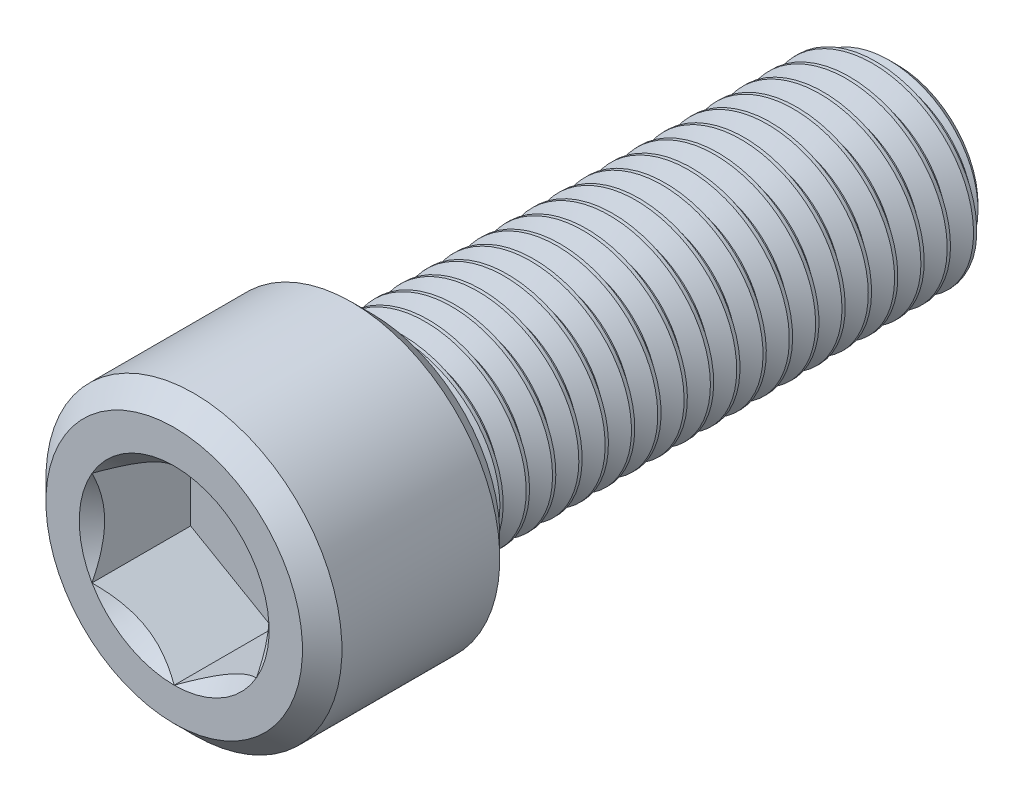
SolidWorks part; units mm, degrees
ref_plane "Front Plane" through (0, 0, 0) normal (0, 0, 1) x (1, 0, 0)
ref_plane "Top Plane" through (0, 0, 0) normal (0, 1, 0) x (1, 0, 0)
ref_plane "Right Plane" through (0, 0, 0) normal (1, 0, 0) x (0, 0, -1)
sketch "Sketch1" plane through (0, 0, 0) normal (1, 0, 0) x (0, 0, -1)
  line L0 (34.925, 0) -> (-34.925, 0) construction
  line L1 (-34.925, 0) -> (-34.925, 12.3825)
  line L2 (-34.925, 12.3825) -> (-33.02, 14.2875)
  line L3 (-33.02, 14.2875) -> (-17.78, 14.2875)
  line L4 (-17.78, 14.2875) -> (-15.875, 12.3825)
  line L5 (-15.875, 12.3825) -> (-15.875, 9.525)
  line L6 (-15.875, 9.525) -> (33.147, 9.525)
  line L7 (33.147, 9.525) -> (34.925, 7.747)
  line L8 (34.925, 7.747) -> (34.925, 0)
  line L9 (34.7662, 9.8) -> (37.3063, 9.8) construction
  line L10 (37.3063, 9.8) -> (36.0363, 7.6003) construction
  line L11 (36.0363, 7.6003) -> (34.7662, 9.8) construction
  line L12 (34.925, 9.525) -> (37.1475, 9.525) construction
  line L13 (36.0363, 9.8) -> (36.0362, 9.525) construction
  line L14 (35.8775, 7.8752) -> (36.195, 7.8752) construction
  line L15 (36.0362, 7.8752) -> (36.0363, 7.6003) construction
  line L16 (34.8456, 9.6625) -> (37.2269, 9.6625)
  line L17 (37.2269, 9.6625) -> (36.195, 7.8752)
  line L18 (36.195, 7.8752) -> (35.8775, 7.8752)
  line L19 (35.8775, 7.8752) -> (34.8456, 9.6625)
  line L20 (33.147, -9.525) -> (28.575, -9.525) construction
  point P3 (-32.0675, 14.2875)
  point P4 (0, 0)
  point P25 (36.0363, 9.6625)
  point P26 (34.925, 9.525)
  point P28 (-18.7325, 14.2875)
  point P29 (-25.4, 14.2875)
  point P33 (28.575, -9.525)
  dimension "Head Ht" = 19.05
  dimension "Screw Size" = 19.05
  dimension "Head Dia" = 28.575
  dimension "D1" = 45
  dimension "D2" = 45
  dimension "D3" = 1.905
  dimension "D4" = 1.905
  dimension "Pitch" = 2.54
  dimension "D5" = 0.3175
  dimension "D6" = 1.778
  dimension "D7" = 4.572
  dimension "Length" = 50.8
  dimension "D8" = 0.9525
  dimension "D9" = 0.9525
sketch "Sketch2" plane through (0, 0, 0) normal (0, 0, 1) x (1, 0, 0)
  line L1 (0, 9.1654) -> (-7.9375, 4.5827)
  line L2 (-7.9375, 4.5827) -> (-7.9375, -4.5827)
  line L3 (-7.9375, -4.5827) -> (0, -9.1654)
  line L4 (0, -9.1654) -> (7.9375, -4.5827)
  line L5 (7.9375, -4.5827) -> (7.9375, 4.5827)
  line L6 (7.9375, 4.5827) -> (0, 9.1654)
  line L8 (0, -14.2875) -> (0, 14.2875) construction
  circle A0 centre (0, 0) radius 7.9375 construction
  circle A1 centre (0, 0) radius 14.2875
  circle A2 centre (0, 0) radius 18.0975 construction
  point P1 (0, 14.2875)
  point P19 (0, 0)
  dimension "D1" = 28.575
  dimension "D3" = 36.195
  dimension "Drive Size" = 15.875
sketch "Sketch3" plane through (0, 0, 0) normal (1, 0, 0) x (0, 0, -1)
  line L0 (34.925, 0) -> (-34.925, 0) construction
  line L1 (-34.925, 0) -> (-34.925, 12.3825) construction
  line L2 (-34.925, 12.3825) -> (-33.02, 14.2875) construction
  line L3 (-33.02, 14.2875) -> (-17.78, 14.2875) construction
  line L4 (-17.78, 14.2875) -> (-15.875, 12.3825) construction
  line L5 (-15.875, 12.3825) -> (-15.875, 9.525) construction
  line L6 (-15.875, 9.525) -> (33.147, 9.525) construction
  line L7 (33.147, 9.525) -> (34.925, 7.747) construction
  line L8 (34.925, 7.747) -> (34.925, 0) construction
  line L9 (34.925, 0) -> (-34.925, 0)
  line L10 (-34.925, 0) -> (-34.925, 12.3825)
  line L11 (-34.925, 12.3825) -> (-33.02, 14.2875)
  line L12 (-33.02, 14.2875) -> (-17.78, 14.2875)
  line L13 (-17.78, 14.2875) -> (-15.875, 12.3825)
  line L14 (-15.875, 12.3825) -> (-15.875, 9.525)
  line L15 (-15.875, 9.525) -> (33.147, 9.525)
  line L16 (33.147, 9.525) -> (34.925, 7.747)
  line L17 (34.925, 7.747) -> (34.925, 0)
revolve "Revolve1" add sketch "Sketch3" angle 360 about L0
sketch "Sketch4" plane through (0, 0, 34.925) normal (0, 0, 1) x (1, 0, 0)
  line L0 (0, -9.1654) -> (7.9375, -4.5827) construction
  line L1 (7.9375, -4.5827) -> (7.9375, 4.5827) construction
  line L2 (7.9375, 4.5827) -> (0, 9.1654) construction
  line L3 (0, 9.1654) -> (-7.9375, 4.5827) construction
  line L4 (-7.9375, 4.5827) -> (-7.9375, -4.5827) construction
  line L5 (-7.9375, -4.5827) -> (0, -9.1654) construction
  line L6 (0, -9.1654) -> (7.9375, -4.5827)
  line L7 (7.9375, -4.5827) -> (7.9375, 4.5827)
  line L8 (7.9375, 4.5827) -> (0, 9.1654)
  line L9 (0, 9.1654) -> (-7.9375, 4.5827)
  line L10 (-7.9375, 4.5827) -> (-7.9375, -4.5827)
  line L11 (-7.9375, -4.5827) -> (0, -9.1654)
extrude "Cut-Extrude1" cut sketch "Sketch4" against normal blind 9.525
sketch "Sketch5" plane through (0, 0, 34.925) normal (0, 0, 1) x (1, 0, 0)
  circle A0 centre (0, 0) radius 9.1654
extrude "Cut-Extrude3" cut sketch "Sketch5" against normal through all draft 45
ref_axis "Center Axis1" through (0, 0, 15.875) along (0, 0, -1)
split "Split1" bodies to split 107 resulting bodies 108 109 split by face at (0, 12.3825, 15.875)
sketch "Sketch6" plane through (0, 0, -34.925) normal (0, 0, -1) x (-1, 0, 0)
  circle A0 centre (0, 0) radius 9.525 construction
  circle A1 centre (0, 0) radius 9.525
curve "Helix/Spiral1" pitch 2.54 height 53.34 radius 9.525 centre (0, 0, -34.925) axis (0, 0, 1) start towards (0, 1, 0)
sketch "Sketch7" plane through (0, 0, 0) normal (1, 0, 0) x (0, 0, -1)
  line L0 (34.8456, 9.6625) -> (37.2269, 9.6625) construction
  line L1 (37.2269, 9.6625) -> (36.195, 7.8752) construction
  line L2 (36.195, 7.8752) -> (35.8775, 7.8752) construction
  line L3 (35.8775, 7.8752) -> (34.8456, 9.6625) construction
  line L4 (34.8456, 9.6625) -> (37.2269, 9.6625)
  line L5 (37.2269, 9.6625) -> (36.195, 7.8752)
  line L6 (36.195, 7.8752) -> (35.8775, 7.8752)
  line L7 (35.8775, 7.8752) -> (34.8456, 9.6625)
sweep "Cut-Sweep1" cut profiles "Sketch7" path "Helix/Spiral1" align with end faces yes
sketch "Sketch8" plane through (0, 0, 15.875) normal (0, 0, -1) x (-1, 0, 0)
  circle A0 centre (0, 0) radius 9.525
  point P3 (0, 9.525)
extrude "Boss-Extrude1" add sketch "Sketch8" along normal blind 2.54 draft 80
equation "\"D3@Sketch1\"=\"Head Ht@Sketch1\"/10"
equation "\"D4@Sketch1\"=\"Head Ht@Sketch1\"/10"
equation "\"D5@Sketch1\"=\"Pitch@Sketch1\"/8"
equation "\"D6@Sketch1\"=\"Pitch@Sketch1\"*.7"
equation "\"D7@Sketch1\"=\"Pitch@Sketch1\"*2.5-\"D6@Sketch1\""
equation "\"D1@Cut-Extrude1\"=\"Head Ht@Sketch1\"/2"
equation "\"D4@Helix/Spiral1\"=\"Pitch@Sketch1\""
equation "\"D3@Helix/Spiral1\"=\"Length@Sketch1\"+\"D4@Helix/Spiral1\""
equation "\"D8@Sketch1\"=\"D4@Sketch1\"/2"
equation "\"D9@Sketch1\"=\"D3@Sketch1\"/2"
